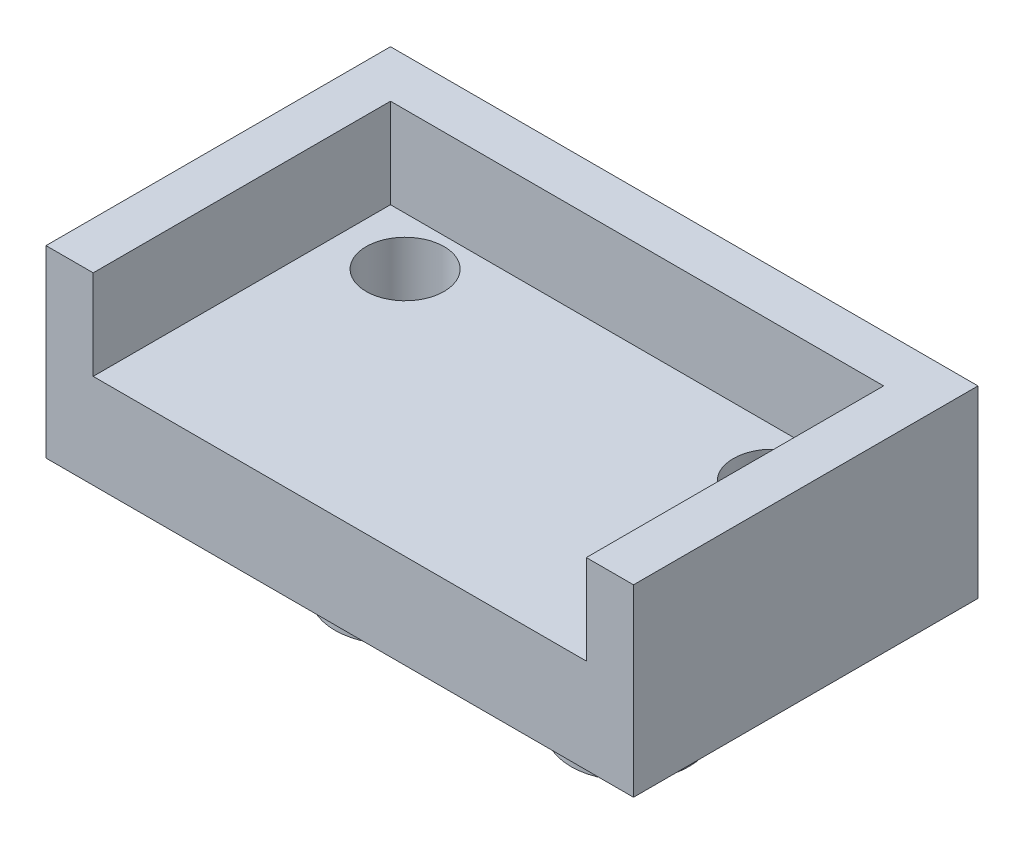
SolidWorks part; units mm, degrees
ref_plane "Front Plane" through (0, 0, 0) normal (0, 0, 1) x (1, 0, 0)
ref_plane "Top Plane" through (0, 0, 0) normal (0, 1, 0) x (1, 0, 0)
ref_plane "Right Plane" through (0, 0, 0) normal (1, 0, 0) x (0, 0, -1)
sketch "Sketch1" plane through (0, 0, 0) normal (0, 1, 0) x (1, 0, 0)
  line L0 (-2, 14.6) -> (22.9, 14.6)
  line L1 (0, 0) -> (20.9, 0)
  line L2 (0, 0) -> (0, 12.6)
  line L3 (0, 12.6) -> (20.9, 12.6)
  line L4 (20.9, 0) -> (20.9, 12.6)
  line L5 (22.9, -2) -> (22.9, 14.6)
  line L6 (-2, -2) -> (22.9, -2)
  line L7 (-2, -2) -> (-2, 14.6)
  line L8 (-2, 0) -> (0, 0)
  line L9 (20.9, 0) -> (22.9, 0)
  dimension "D1" = 12.6
  dimension "D2" = 20.9
  dimension "D3" = 2
extrude "Boss-Extrude1" add sketch "Sketch1" along normal blind 3.8 contours L4 L9 L5 L0 L7 L8 L2 L3 region at (10.45, 0, -14.3114)
extrude "Boss-Extrude2" add sketch "Sketch1<3>" against normal blind 4 contours L1 L4 L3 L2 | L4 L9 L5 L0 L7 L8 L2 L3 region at (10.45, 0, -14.3114) region at (10.45, 0, -6.3)
sketch "Sketch1<3>" plane through (0, 0, 0) normal (0, 1, 0) x (1, 0, 0) same geometry as "Sketch1"
sketch "Sketch3" plane through (0, -4, 0) normal (0, -1, 0) x (1, 0, 0)
  line L0 (10.45, 0) -> (10.45, -14.6) construction
  line L1 (-2, 0) -> (22.9, 0) construction
  line L2 (-2, -14.6) -> (22.9, -14.6) construction
  line L3 (5.45, -7.3) -> (10.45, -7.3) construction
  circle A0 centre (5.45, -7.3) radius 2.5
  circle A1 centre (15.45, -7.3) radius 2.5
  dimension "D1" = 5
  dimension "D2" = 5
extrude "Boss-Extrude4" add sketch "Sketch3" along normal blind 5
sketch "Sketch2" plane through (0, 0, 0) normal (0, 1, 0) x (1, 0, 0)
  line L0 (0, 0) -> (0, 12.6) construction
  line L1 (0, 12.6) -> (20.9, 12.6) construction
  line L2 (20.9, 0) -> (20.9, 12.6) construction
  line L4 (2.6, 11.7) -> (2.6, 8.7) construction
  line L5 (2.6, 8.7) -> (18.3, 8.7) construction
  line L6 (18.3, 8.7) -> (18.3, 11.7) construction
  line L7 (2.1, 11.7) -> (2.1, 8.7)
  line L8 (18.8, 8.7) -> (18.8, 11.7)
  line L9 (3.1, 11.7) -> (3.1, 8.7)
  line L10 (17.8, 8.7) -> (17.8, 11.7)
  circle A0 centre (2.6, 10.2) radius 1.5
  circle A1 centre (18.3, 10.2) radius 1.5
  dimension "D1" = 3
  dimension "D2" = 2.6
  dimension "D3" = 2.4
  dimension "D4" = 2.6
  dimension "D5" = 0.5
  dimension "D6" = 0.5
extrude "Boss-Extrude3" [suppressed] add sketch "Sketch2" along normal blind 2 contours L9 A0 | L7 A0 | L8 A1 | L10 A1
sketch "Sketch5" plane through (0, 0, 0) normal (0, 1, 0) x (1, 0, 0)
  line L0 (10.45, 12.6) -> (10.45, -1.1994) construction
  line L1 (-0.105, -2.54) -> (21.005, -2.54)
  line L2 (-0.105, -2.54) -> (-0.105, 13.21)
  line L3 (-0.105, 13.21) -> (21.005, 13.21)
  line L4 (21.005, -2.54) -> (21.005, 13.21)
  line L5 (-0.105, -2.54) -> (21.005, 13.21) construction
  line L6 (-0.105, 13.21) -> (21.005, -2.54) construction
  line L8 (0, 0) -> (20.9, 0) construction
  line L9 (20.9, 0) -> (20.9, 12.6) construction
  line L10 (0, 0) -> (0, 12.6) construction
  circle A0 centre (2.67, 10.55) radius 1.65
  circle A1 centre (18.23, 10.55) radius 1.65
  point P0 (10.45, 5.335)
  dimension "D4" = 3.3
  dimension "D1" = 2.54
  dimension "D2" = 21.11
  dimension "D3" = 15.75
  dimension "D5" = 15.56
  dimension "D6" = 2.66
extrude "Cut-Extrude1" cut sketch "Sketch5" against normal up to surface (4 mm away) contours A0 | A1 up to face at (15.45, -4, -4.8)
